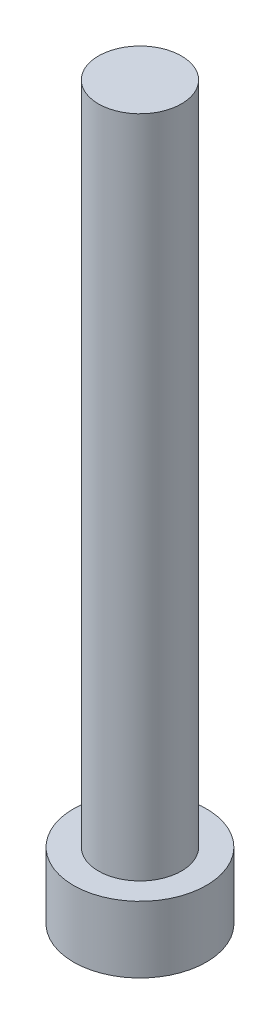
SolidWorks part; units mm, degrees
ref_plane "Front Plane" through (0, 0, 0) normal (0, 0, 1) x (1, 0, 0)
ref_plane "Top Plane" through (0, 0, 0) normal (0, 1, 0) x (1, 0, 0)
ref_plane "Right Plane" through (0, 0, 0) normal (1, 0, 0) x (0, 0, -1)
sketch "Sketch1" plane through (0, 0, 0) normal (0, 1, 0) x (1, 0, 0)
  circle A0 centre (0, 0) radius 1.25
  circle A1 centre (0, 0) radius 2
  dimension "D1" = 2.5
  dimension "D2" = 4
extrude "Boss-Extrude1" add sketch "Sketch1" along normal blind 20 contours A0
extrude "Boss-Extrude2" add sketch "Sketch1<4>" against normal blind 2 contours A1
sketch "Sketch1<4>" plane through (0, 0, 0) normal (0, 1, 0) x (1, 0, 0) same geometry as "Sketch1"
